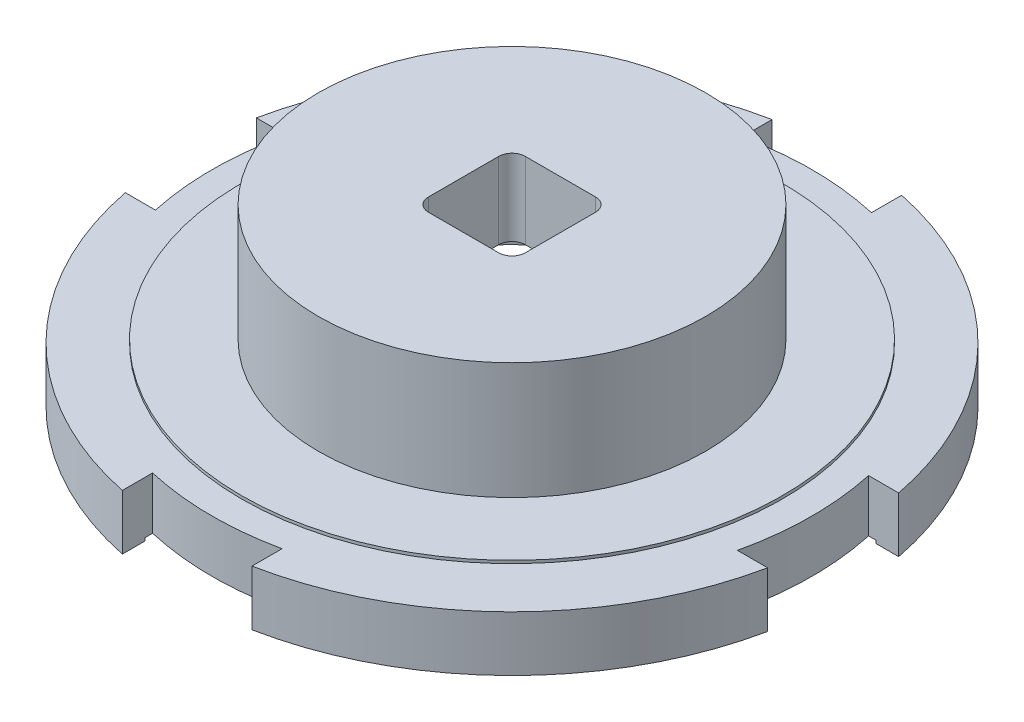
SolidWorks part; units mm, degrees
note: '?' marks a value the reader was unsure of.
ref_plane "Front Plane" through (0, 0, 0) normal (0, 0, 1) x (1, 0, 0)
ref_plane "Top Plane" through (0, 0, 0) normal (0, 1, 0) x (1, 0, 0)
ref_plane "Right Plane" through (0, 0, 0) normal (1, 0, 0) x (0, 0, -1)
sketch "Sketch1" plane through (0, 0, 0) normal (0, 1, 0) x (1, 0, 0)
  line L0 (30.2899, 6.5405) -> (33.4017, 6.5405)
  line L1 (30.2051, -6.9215) -> (33.3248, -6.9215)
  line L2 (-55, 0) -> (55, 0) construction
  line L3 (6.5405, -30.2899) -> (6.5405, -33.4017)
  line L4 (-6.9215, -30.2051) -> (-6.9215, -33.3248)
  line L5 (-30.2899, -6.5405) -> (-33.4017, -6.5405)
  line L6 (-30.2051, 6.9215) -> (-33.3248, 6.9215)
  line L7 (-6.5405, 30.2899) -> (-6.5405, 33.4017)
  line L8 (6.9215, 30.2051) -> (6.9215, 33.3248)
  line L9 (-5, 5) -> (-5, -5)
  line L10 (-5, -5) -> (5, -5)
  line L11 (5, -5) -> (5, 5)
  line L12 (5, 5) -> (-5, 5)
  line L13 (0, -55) -> (0, 55) construction
  arc A1 (-33.4017, -6.5405) -> (-6.9215, -33.3248) centre (0, 0) ccw
  arc A3 (-30.2051, 6.9215) -> (-30.2899, -6.5405) centre (0, 0) ccw
  arc A4 (6.9215, 30.2051) -> (-6.5405, 30.2899) centre (0, 0) ccw
  arc A5 (30.2051, -6.9215) -> (30.2899, 6.5405) centre (0, 0) ccw
  arc A6 (-6.9215, -30.2051) -> (6.5405, -30.2899) centre (0, 0) ccw
  arc A7 (6.5405, -33.4017) -> (33.3248, -6.9215) centre (0, 0) ccw
  arc A8 (33.4017, 6.5405) -> (6.9215, 33.3248) centre (0, 0) ccw
  arc A9 (-6.5405, 33.4017) -> (-33.3248, 6.9215) centre (0, 0) ccw
  point P11 (0, 5)
  point P26 (0, 0)
  point P28 (5, 0)
  dimension "D1" = 68.072
  dimension "D2" = 61.976
  dimension "D6" = 10
  dimension "D3" = 13.462
  dimension "D4" = 6.5405
  dimension "D7" = 10
  dimension "D5" = 4
ref_axis "Axis1" through (41.0751, 0, 0) along (-1, 0, 0)?
ref_plane "Plane2" through (0, 0, 0) normal (0, -0.9903, 0.1392) x (-1, 0, 0)
ref_plane "Plane3" through (0, 6.2882, -0.8837) normal (0, -0.9903, 0.1392) x (-1, 0, 0)
extrude "Boss-Extrude2" add sketch "Sketch1" along normal blind 6
sketch "Sketch2" plane through (0, 0, 0) normal (0, -1, 0) x (1, 0, 0)
  line L3 (17.3777, -10.033) -> (-0.2866, -40.6283)
  line L4 (-4.5397, -40.3749) -> (8.1962, -18.3157)
  line L5 (3.2131, 0) -> (-3.2131, 0) construction
  arc A3 (8.1962, -18.3157) -> (17.3777, -10.033) centre (0, 0) cw
  arc A4 (-0.2866, -40.6283) -> (-4.5397, -40.3749) centre (0, 0) cw
  point P4 (8.5456, -25.3307)
  dimension "D1" = 20.066
  dimension "D2" = 3.81
  dimension "D3" = 60
extrude "Cut-Extrude1" cut sketch "Sketch2" against normal blind 3.81
sketch "Sketch3" plane through (0, 0, 0) normal (0, -1, 0) x (1, 0, 0)
  circle A0 centre (0, 0) radius 31.75
extrude "Cut-Extrude2" cut sketch "Sketch3" against normal blind 0.3
sketch "Sketch4" plane through (0, 6, 0) normal (0, 1, 0) x (1, 0, 0)
  circle A0 centre (0, 0) radius 20.01
  dimension "D1" = 40.02
extrude "Boss-Extrude3" add sketch "Sketch4" along normal blind 12.065
sketch "Sketch5" plane through (0, 3.81, 0) normal (0, -1, 0) x (1, 0, 0)
  circle A0 centre (0, 0) radius 15.875
extrude "Cut-Extrude3" cut sketch "Sketch5" against normal blind 6.35
fillet "Fillet1" radius 1.3716 4 edges at (5, 14.1125, -5) (5, 14.1125, 5) (-5, 14.1125, 5) (-5, 14.1125, -5)
sketch "Sketch6" plane through (0, 6, 0) normal (0, 1, 0) x (1, 0, 0)
  circle A0 centre (0, 0) radius 27.94
  circle A1 centre (0, 0) radius 54.9701
  dimension "D1" = 55.88
extrude "Cut-Extrude4" cut sketch "Sketch6" against normal blind 0.3
